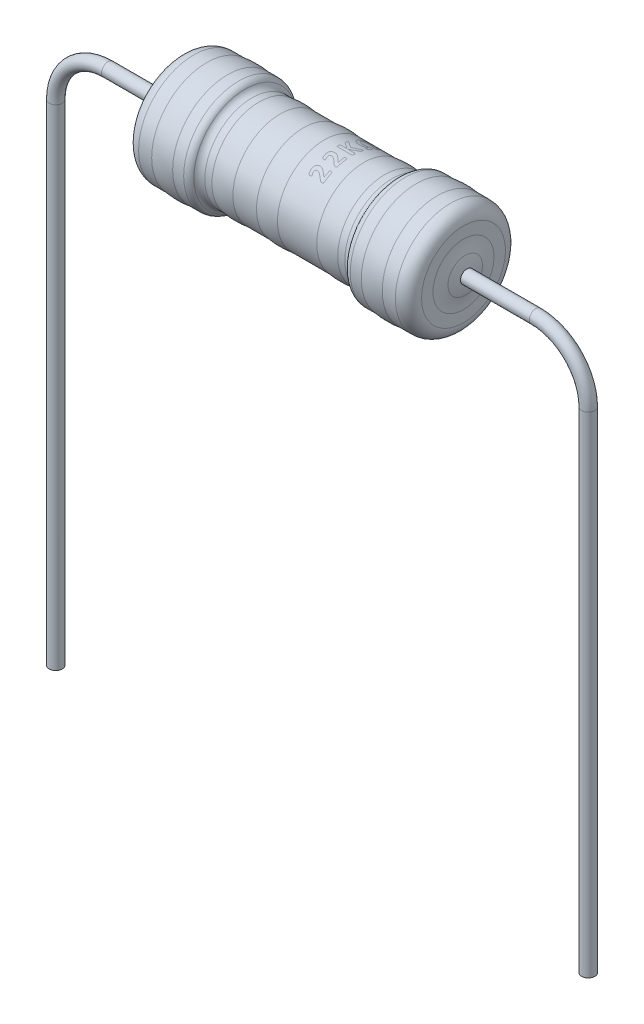
SolidWorks part; units mm, degrees
ref_plane "Front Plane" through (0, 0, 0) normal (0, 0, 1) x (1, 0, 0)
ref_plane "Top Plane" through (0, 0, 0) normal (0, 1, 0) x (1, 0, 0)
ref_plane "Right Plane" through (0, 0, 0) normal (1, 0, 0) x (0, 0, -1)
sketch "Sketch Set Wire Width" plane through (0, 0, 0) normal (0, 0, 1) x (1, 0, 0)
  line L0 (-8.16, 0) -> (8.16, 0)
  line L1 (-10.16, -2) -> (-10.16, -20.6984)
  line L2 (10.16, -2) -> (10.16, -20.6984)
  line L3 (-10.16, -20.6984) -> (10.16, -20.6984) construction
  line L4 (0, 0) -> (0, -20.6984) construction
  arc A0 (-8.16, 0) -> (-10.16, -2) centre (-8.16, -2) ccw
  arc A1 (8.16, 0) -> (10.16, -2) centre (8.16, -2) cw
  dimension "D2" = 2
  dimension "D3" = 60
  dimension "D1" = 20.32
sketch "Sketch Wire Diameter" plane through (0, 0, 0) normal (1, 0, 0) x (0, 0, -1)
  circle A0 centre (0, 0) radius 0.25
  dimension "D1" = 0.5
sweep "SET WIRE LENGTH" add profiles "Sketch Wire Diameter" path "Sketch Set Wire Width"
sketch "Sketch3" plane through (0, 0, 0) normal (0, 0, 1) x (1, 0, 0)
  line L0 (-5.4, 0) -> (5.4, 0)
  line L1 (0, 0) -> (0, 1.8) construction
  line L2 (-2.9, 1.8) -> (2.9, 1.8)
  line L3 (-5.4, 0) -> (-5.4, 1.6)
  line L4 (-4.9, 2.1) -> (-3.18, 2.1)
  line L5 (-2.9, 1.82) -> (-2.9, 1.8)
  line L6 (5.4, 0) -> (5.4, 1.6)
  line L7 (4.9, 2.1) -> (3.18, 2.1)
  line L8 (2.9, 1.82) -> (2.9, 1.8)
  arc A0 (-5.4, 1.6) -> (-4.9, 2.1) centre (-4.9, 1.6) cw
  arc A1 (5.4, 1.6) -> (4.9, 2.1) centre (4.9, 1.6) ccw
  arc A2 (-3.18, 2.1) -> (-2.9, 1.82) centre (-3.18, 1.82) cw
  arc A3 (3.18, 2.1) -> (2.9, 1.82) centre (3.18, 1.82) ccw
  dimension "D5" = 0.5
  dimension "D6" = 0.28
  dimension "D1" = 10.8
  dimension "D2" = 5.8
  dimension "D3" = 1.8
  dimension "D4" = 2.1
revolve "Revolve2" add sketch "Sketch3" angle 360 about L0
fillet "Fillet1" radius 0.3 2 edges at (2.9, 0, 1.8) (-2.9, 0, 1.8)
sketch "Sketch5" plane through (0, 0, 0) normal (0, 0, 1) x (1, 0, 0)
  line L0 (0, 0) -> (2, 0) construction
  line L1 (0, 0) -> (-0.3, 0) construction
  line L2 (-0.3, 0) -> (-2, 0) construction
  line L3 (-2, 0) -> (-4, 0) construction
  line L4 (2, 0) -> (4, 0) construction
  line L5 (-4, 0) -> (-4, 2.1) construction
  line L6 (-0.3, 0) -> (-0.3, 1.8) construction
  line L7 (-2, 0) -> (-2, 1.8) construction
  line L8 (2, 0) -> (2, 1.8) construction
  line L9 (4, 0) -> (4, 2.1) construction
  line L10 (-4, 2.1) -> (-4, 2.13) construction
  line L11 (-4.9, 2.1) -> (-3.18, 2.1) construction
  line L12 (4.9, 2.1) -> (3.18, 2.1) construction
  line L13 (-2.9, 1.8) -> (2.9, 1.8) construction
  line L14 (-2, 1.8) -> (-2, 1.83) construction
  line L17 (-4.4, 2.1) -> (-3.6, 2.1)
  line L19 (-5.4, 0) -> (5.4, 0) construction
  line L22 (-2.4, 1.8) -> (-1.6, 1.8) construction
  line L26 (-0.7, 1.8) -> (0.1, 1.8) construction
  line L30 (1.6, 1.8) -> (2.4, 1.8) construction
  line L34 (3.6, 2.1) -> (4.4, 2.1) construction
  line L36 (-0.3, 1.8) -> (-0.3, 1.83) construction
  line L37 (2, 1.8) -> (2, 1.83) construction
  line L38 (4, 2.1) -> (4, 2.13) construction
  arc A0 (-4.4, 2.1) -> (-3.6, 2.1) centre (-4, -0.5517) cw
  arc A1 (-2.4, 1.8) -> (-1.6, 1.8) centre (-2, -0.8517) cw construction
  arc A2 (-0.7, 1.8) -> (0.1, 1.8) centre (-0.3, -0.8517) cw construction
  arc A3 (1.6, 1.8) -> (2.4, 1.8) centre (2, -0.8517) cw construction
  arc A4 (3.6, 2.1) -> (4.4, 2.1) centre (4, -0.5517) cw construction
  dimension "D3" = 0.8
  dimension "D1" = 4
  dimension "D2" = 4
  dimension "D4" = 0.03
  dimension "D5" = 2
  dimension "D6" = 2
  dimension "D7" = 1.7
revolve "Band 1" add sketch "Sketch5" angle 360 about L2
sketch "Sketch8" plane through (0, 0, 0) normal (0, 0, 1) x (1, 0, 0)
  line L0 (-2.4, 1.8) -> (-1.6, 1.8) construction
  line L1 (-2.4, 1.8) -> (-1.6, 1.8)
  arc A0 (-1.6, 1.8) -> (-2.4, 1.8) centre (-2, -0.8517) ccw construction
  arc A1 (-1.6, 1.8) -> (-2.4, 1.8) centre (-2, -0.8517) ccw
revolve "Band 2" add sketch "Sketch8" angle 360 about L2
sketch "Sketch9" plane through (0, 0, 0) normal (0, 0, 1) x (1, 0, 0)
  line L0 (-0.7, 1.8) -> (0.1, 1.8) construction
  line L1 (-0.7, 1.8) -> (0.1, 1.8)
  arc A0 (0.1, 1.8) -> (-0.7, 1.8) centre (-0.3, -0.8517) ccw construction
  arc A1 (0.1, 1.8) -> (-0.7, 1.8) centre (-0.3, -0.8517) ccw
revolve "Band 3" add sketch "Sketch9" angle 360 about L2
sketch "Sketch10" plane through (0, 0, 0) normal (0, 0, 1) x (1, 0, 0)
  line L0 (1.6, 1.8) -> (2.4, 1.8) construction
  line L1 (1.6, 1.8) -> (2.4, 1.8)
  arc A0 (2.4, 1.8) -> (1.6, 1.8) centre (2, -0.8517) ccw construction
  arc A1 (2.4, 1.8) -> (1.6, 1.8) centre (2, -0.8517) ccw
revolve "Band 4" add sketch "Sketch10" angle 360 about L0
sketch "Sketch11" plane through (0, 0, 0) normal (0, 0, 1) x (1, 0, 0)
  line L0 (3.6, 2.1) -> (4.4, 2.1) construction
  line L1 (3.6, 2.1) -> (4.4, 2.1)
  arc A0 (4.4, 2.1) -> (3.6, 2.1) centre (4, -0.5517) ccw construction
  arc A1 (4.4, 2.1) -> (3.6, 2.1) centre (4, -0.5517) ccw
revolve "Band 5" add sketch "Sketch11" angle 360 about L4
sketch "Sketch12" plane through (0, 0, 0) normal (0, 0, 1) x (1, 0, 0)
  line L0 (-5.35, 0) -> (5.35, 0) construction
  line L1 (-5.35, 1) -> (-5.35, 0)
  line L2 (5.35, 1) -> (5.35, 0)
  line L3 (-5.35, 0) -> (-5.55, 0)
  line L4 (5.35, 0) -> (5.55, 0)
  arc A0 (-5.35, 1) -> (-5.55, 0) centre (-2.95, 0) ccw
  arc A1 (5.35, 1) -> (5.55, 0) centre (2.95, 0) cw
  dimension "D3" = 0.2
  dimension "D4" = 2.6
  dimension "D1" = 10.7
  dimension "D2" = 1
revolve "Revolve10" add sketch "Sketch12" angle 360 about L0
fillet "Fillet2" radius 2 2 edges at (5.4, 0, 0.8703) (-5.4, 0, -0.8703)
ref_plane "Plane2" through (0, 3, 0) normal (0, 1, 0) x (1, 0, 0)
sketch "Sketch13" plane through (0, 3, 0) normal (0, 1, 0) x (1, 0, 0)
  line L0 (0, 0) -> (1.15, 0) construction
  line L1 (1.15, 1.75) -> (1.15, -1.75) construction
  text T0 "22KΩ" font "Calibri" height 0.6
  dimension "D1" = 3.5
  dimension "D2" = 1.15
wrap "Wrap1" sketch "Sketch13" wrap type scribe source sketch "Sketch13" face at (0.1, 1.8, 0)
